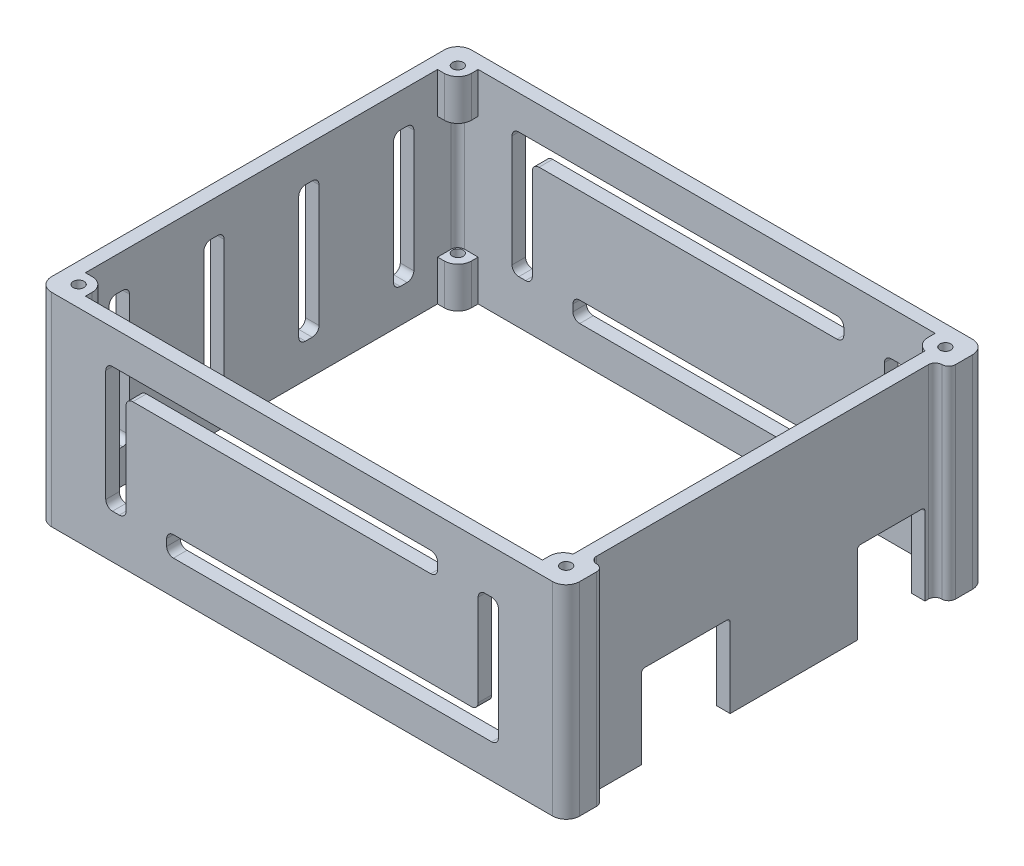
SolidWorks part; units mm, degrees
ref_plane "Front" through (0, 0, 0) normal (0, 0, 1) x (1, 0, 0)
ref_plane "Top" through (0, 0, 0) normal (0, 1, 0) x (1, 0, 0)
ref_plane "Right" through (0, 0, 0) normal (1, 0, 0) x (0, 0, -1)
sketch "Sketch4" plane through (0, 0, 0) normal (0, 1, 0) x (1, 0, 0)
  line L1 (-38, -31) -> (40, -31)
  line L2 (-38, -31) -> (-38, 31)
  line L3 (-38, 31) -> (40, 31)
  line L5 (-36, -29) -> (36, -29)
  line L6 (-36, -29) -> (-36, 29)
  line L7 (-36, 29) -> (36, 29)
  line L10 (36, -29) -> (36, 29)
  line L13 (40, 31) -> (40, 25.5)
  line L14 (40, 25.5) -> (38, 25.5)
  line L15 (38, 25.5) -> (38, -25.5)
  line L16 (38, -25.5) -> (40, -25.5)
  line L17 (40, -25.5) -> (40, -31)
  line L18 (60.7482, 0) -> (-81.0515, 0) construction
  line L19 (0, -50.7627) -> (0, 56.135) construction
  dimension "D1" = 2
  dimension "D2" = 2
  dimension "D3" = 2
  dimension "D5" = 62
  dimension "D9" = 78
  dimension "D10" = 5.5
  dimension "D8" = 2
  dimension "D4" = 4
extrude "Boss-Extrude3" add sketch "Sketch4" along normal blind 30
ref_plane "Plane1" through (0, 15, 0) normal (0, -1, 0) x (-1, 0, 0)
sketch "Sketch5" plane through (38, 0, 0) normal (1, 0, 0) x (0, 0, -1)
  line L1 (-17.88, 12.2) -> (-4.78, 12.2)
  line L2 (-17.88, 12.2) -> (-17.88, 0)
  line L3 (-17.88, 0) -> (-4.78, 0)
  line L4 (-4.78, 12.2) -> (-4.78, 0)
  line L8 (14, 12) -> (24, 12)
  line L9 (14, 12) -> (14, 0)
  line L10 (14, 0) -> (24, 0)
  line L11 (24, 12) -> (24, 0)
  line L16 (-31, 30) -> (-31, 0) construction
  line L17 (31, 30) -> (31, 0) construction
  line L18 (-25.5, 0) -> (25.5, 0) construction
  dimension "D1" = 12.2
  dimension "D2" = 13.1
  dimension "D3" = 7
  dimension "D4" = 13.12
  dimension "D5" = 10
  dimension "D7" = 12
extrude "Cut-Extrude2" cut sketch "Sketch5" against normal blind 13
sketch "Sketch15" plane through (-38, 0, 0) normal (-1, 0, 0) x (0, 0, 1)
  line L0 (-22.5, 25) -> (-19.5, 5) construction
  line L1 (-21.5, 25) -> (-20.5, 25)
  line L2 (-22.5, 24) -> (-22.5, 6)
  line L3 (-21.5, 5) -> (-20.5, 5)
  line L4 (-19.5, 24) -> (-19.5, 6)
  line L5 (-19.5, 25) -> (-22.5, 5) construction
  line L6 (-31, 0) -> (31, 0) construction
  line L7 (-31, 30) -> (31, 30) construction
  line L8 (-21.9872, 15) -> (-14.6049, 15) construction
  line L11 (0, 30.1548) -> (0, -14.5619) construction
  line L12 (-8.5, 25) -> (-5.5, 5) construction
  line L13 (-7.5, 25) -> (-6.5, 25)
  line L14 (-8.5, 24) -> (-8.5, 6)
  line L15 (-7.5, 5) -> (-6.5, 5)
  line L16 (-5.5, 24) -> (-5.5, 6)
  line L17 (-5.5, 25) -> (-8.5, 5) construction
  line L18 (-11.0945, 15) -> (-3.7122, 15) construction
  arc A0 (-20.5, 5) -> (-19.5, 6) centre (-20.5, 6) ccw
  arc A1 (-22.5, 6) -> (-21.5, 5) centre (-21.5, 6) ccw
  arc A2 (-20.5, 25) -> (-19.5, 24) centre (-20.5, 24) cw
  arc A3 (-21.5, 25) -> (-22.5, 24) centre (-21.5, 24) ccw
  arc A4 (-6.5, 5) -> (-5.5, 6) centre (-6.5, 6) ccw
  arc A5 (-8.5, 6) -> (-7.5, 5) centre (-7.5, 6) ccw
  arc A6 (-6.5, 25) -> (-5.5, 24) centre (-6.5, 24) cw
  arc A7 (-7.5, 25) -> (-8.5, 24) centre (-7.5, 24) ccw
  point P4 (-21, 15)
  point P30 (-7, 15)
  dimension "D1" = 1
  dimension "D4" = 1
  dimension "D2" = 3
  dimension "D3" = 20
  dimension "D5" = 3
  dimension "D6" = 20
  dimension "D7" = 7
  dimension "D8" = 14
extrude "Cut-Extrude4" cut sketch "Sketch15" against normal up to next
mirror "Mirror1" about plane through (0, 0, 0) normal (0, 0, 1) of "Cut-Extrude4"
sketch "Sketch14" plane through (0, 0, -31) normal (0, 0, 1) x (1, 0, 0)
  line L0 (-28, 7.5) -> (-28, 24)
  line L1 (-27, 25) -> (20, 25)
  line L2 (21, 24) -> (21, 23)
  line L3 (20, 22) -> (-24, 22)
  line L4 (-25, 21) -> (-25, 7.5)
  line L5 (-26, 6.5) -> (-27, 6.5)
  line L6 (27, 22.5) -> (27, 9)
  line L7 (26, 8) -> (-18, 8)
  line L8 (-19, 7) -> (-19, 6)
  line L9 (-18, 5) -> (29, 5)
  line L10 (30, 6) -> (30, 22.5)
  line L11 (29, 23.5) -> (28, 23.5)
  line L14 (-38, 30) -> (40, 30) construction
  line L16 (14.1221, 23.5) -> (20.4912, 23.5) construction
  line L17 (-16.6659, 6.5) -> (-23.9885, 6.5) construction
  line L18 (-38, 30) -> (-38, 0) construction
  line L19 (40, 0) -> (-38, 0) construction
  line L21 (40, 30) -> (40, 0) construction
  arc A0 (-18, 8) -> (-19, 7) centre (-18, 7) ccw
  arc A1 (-19, 6) -> (-18, 5) centre (-18, 6) ccw
  arc A2 (29, 5) -> (30, 6) centre (29, 6) ccw
  arc A3 (27, 9) -> (26, 8) centre (26, 9) cw
  arc A4 (30, 22.5) -> (29, 23.5) centre (29, 22.5) ccw
  arc A5 (27, 22.5) -> (28, 23.5) centre (28, 22.5) cw
  arc A6 (20, 25) -> (21, 24) centre (20, 24) cw
  arc A7 (21, 23) -> (20, 22) centre (20, 23) cw
  arc A8 (-28, 7.5) -> (-27, 6.5) centre (-27, 7.5) ccw
  arc A9 (-25, 7.5) -> (-26, 6.5) centre (-26, 7.5) cw
  arc A10 (-24, 22) -> (-25, 21) centre (-24, 21) ccw
  arc A11 (-28, 24) -> (-27, 25) centre (-27, 24) cw
  point P32 (-26.8, 8)
  point P53 (21, 23.5)
  dimension "D1" = 1
  dimension "D2" = 3
  dimension "D3" = 3
  dimension "D4" = 3
  dimension "D5" = 3
  dimension "D8" = 5
  dimension "D10" = 6
  dimension "D11" = 6
  dimension "D6" = 10
  dimension "D7" = 5
  dimension "D9" = 10
extrude "Cut-Extrude3" cut sketch "Sketch14" along normal through all
sketch "Sketch21" plane through (0, 0, 0) normal (0, -1, 0) x (1, 0, 0)
  line L0 (-36, 29) -> (36, 29) construction
  line L1 (-36, 29) -> (-33, 29)
  line L2 (-36, 29) -> (-36, 26)
  line L3 (-36, 26) -> (-33, 26)
  line L4 (-33, 29) -> (-33, 26)
  line L5 (36, 29) -> (34.5, 29)
  line L6 (36, 29) -> (36, 26)
  line L7 (36, 26) -> (34.5, 26)
  line L8 (34.5, 29) -> (34.5, 26)
  line L9 (36, -29) -> (34.5, -29)
  line L10 (36, -29) -> (36, -26)
  line L11 (36, -26) -> (34.5, -26)
  line L12 (34.5, -29) -> (34.5, -26)
  line L13 (-36, -29) -> (-33, -29)
  line L14 (-36, -29) -> (-36, -26)
  line L15 (-36, -26) -> (-33, -26)
  line L16 (-33, -29) -> (-33, -26)
  line L17 (36, 29) -> (36, 17.88) construction
  line L18 (36, -29) -> (-36, -29) construction
  dimension "D1" = 3
  dimension "D2" = 1.5
  dimension "D3" = 3
extrude "Boss-Extrude5" add sketch "Sketch21" against normal blind 6
hole_wizard "M2 Tapped Hole1" positions "Sketch22" profile "Sketch24" tap size "M2" standard "ISO" end condition up to next
sketch "Sketch22" plane through (0, 0, 0) normal (0, -1, 0) x (-1, 0, 0)
  line L1 (-37, -28) -> (35, -28)
  line L2 (-37, -28) -> (-37, 28)
  line L3 (-37, 28) -> (35, 28)
  line L4 (35, -28) -> (35, 28)
  line L5 (38, 31) -> (38, -31) construction
  line L6 (-40, 31) -> (38, 31) construction
  line L7 (38, -31) -> (-40, -31) construction
  line L8 (-40, 25.5) -> (-40, 31) construction
  point P0 (35, 28)
  point P2 (35, -28)
  point P4 (-37, -28)
  point P6 (-37, 28)
  point P134 (-40, 28.25)
  dimension "D2" = 3
  dimension "D3" = 3
  dimension "D4" = 3
  dimension "D1" = 3
sketch "Sketch24" plane through (-35, 0, -28) normal (1, 0, 0) x (0, 0, -1)
  line L0 (0, 0) -> (0, 30)
  line L1 (0, 30) -> (0.8, 30)
  line L2 (0.8, 30) -> (0.8, 0)
  line L5 (0.8, 0) -> (0, 0)
  line L11 (0, -6.35) -> (0, 107.95) construction
  dimension "Thru Tap Drill Dia." = 1.6
  dimension "Thru Tap Drill Depth" = 30
cosmetic thread "Hole Thread17" parameters "D2"=2
cosmetic thread "Hole Thread18" parameters "D2"=2
cosmetic thread "Hole Thread19" parameters "D2"=2
cosmetic thread "Hole Thread20" parameters "D2"=2
fillet "Fillet1" radius 1 8 edges at (-36, 18, 29) (-36, 18, -29) (36, 18, 29) (36, 18, -29) (40, 15, -25.5) (38, 15, -25.5) (38, 15, 25.5) (40, 15, 25.5)
fillet "Fillet4" radius 0.5 4 edges at (37, 12.2, 17.88) (37, 12, -14) (37, 12, -24) (37, 12.2, 4.78)
mirror "Mirror2" about plane through (0, 15, 0) normal (0, -1, 0) of "M2 Tapped Hole1", "Boss-Extrude5"
fillet "Fillet5" radius 2 12 edges at (-38, 15, 31) (-38, 15, -31) (-33, 3, 26) (-33, 3, -26) (34.5, 3, -26) (34.5, 3, 26) (40, 15, 31) (40, 15, -31) (34.5, 27, -26) (-33, 27, -26) (-33, 27, 26) (34.5, 27, 26)
equation "\"D2@Sketch4\"=\"D1@Sketch4\""
equation "\"D3@Sketch4\"=\"D1@Sketch4\""
equation "\"D3@Sketch14\"=\"D2@Sketch14\""
equation "\"D4@Sketch14\"=\"D2@Sketch14\""
equation "\"D5@Sketch14\"=\"D2@Sketch14\""
equation "\"D3@Sketch22\"=\"D2@Sketch22\""
